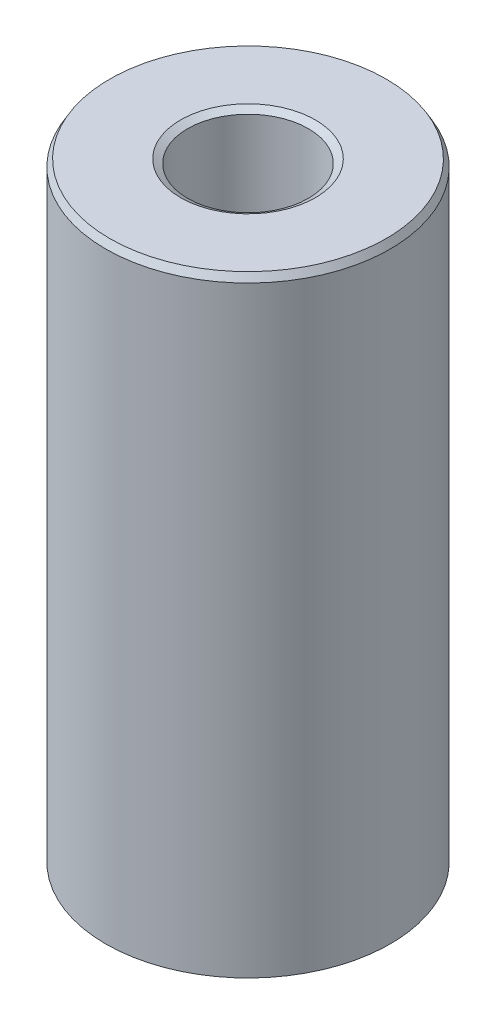
SolidWorks part; units mm, degrees
ref_plane "Front Plane" through (0, 0, 0) normal (0, 0, 1) x (1, 0, 0)
ref_plane "Top Plane" through (0, 0, 0) normal (0, 1, 0) x (1, 0, 0)
ref_plane "Right Plane" through (0, 0, 0) normal (1, 0, 0) x (0, 0, -1)
sketch "Sketch1" plane through (0, 0, 0) normal (0, 1, 0) x (1, 0, 0)
  circle A0 centre (0, 0) radius 42.5
  dimension "SLEEVE_OD" = 85
extrude "Boss-Extrude1" add sketch "Sketch1" along normal blind 183.1145
sketch "Sketch2" plane through (0, 0, 0) normal (0, 1, 0) x (1, 0, 0)
  circle A0 centre (0, 0) radius 18.041
  dimension "BORE_D" = 36.082
extrude "Cut-Extrude1" cut sketch "Sketch2" along normal through all
chamfer "Chamfer1" distance 2.0995 angle 30 4 edges at (0, 183.1145, 18.041) (0, 0, 18.041) (0, 0, 42.5) (0, 183.1145, 42.5) first distance on face at (0, 183.1145, 18.041) first distance on face at (0, 0, 18.041) first distance on face at (0, 183.1145, 42.5)
